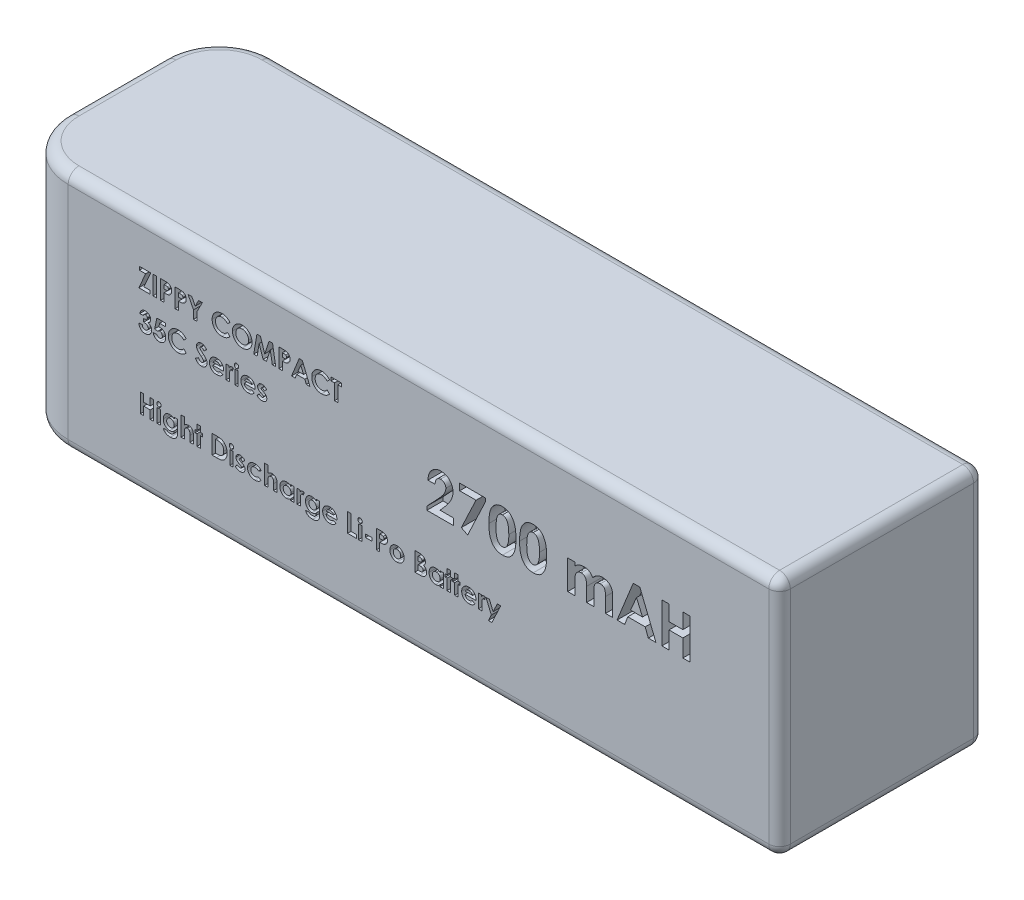
SolidWorks part; units mm, degrees
material "PPS"
ref_plane "Plan de face" through (0, 0, 0) normal (0, 0, 1) x (1, 0, 0)
ref_plane "Plan de dessus" through (0, 0, 0) normal (0, 1, 0) x (1, 0, 0)
ref_plane "Plan de droite" through (0, 0, 0) normal (1, 0, 0) x (0, 0, -1)
sketch "Esquisse1" plane through (0, 0, 0) normal (0, 0, 1) x (1, 0, 0)
  line L1 (0, 0) -> (142, 0)
  line L2 (0, 0) -> (0, 45)
  line L3 (0, 45) -> (142, 45)
  line L4 (142, 0) -> (142, 45)
  dimension "D1" = 142
  dimension "D2" = 45
extrude "Boss.-Extru.1" add sketch "Esquisse1" along normal blind 38
fillet "Congé2" radius 10 2 edges at (0, 22.5, 38) (0, 22.5, 0)
fillet "Congé3" radius 2 14 edges at (142, 22.5, 0) (142, 0, 19) (76, 0, 0) (2.9289, 0, 2.9289) (2.9289, 0, 35.0711) (0, 0, 19) (142, 22.5, 38) (76, 0, 38) (2.9289, 45, 2.9289) (76, 45, 0) (142, 45, 19) (76, 45, 38) (2.9289, 45, 35.0711) (0, 45, 19)
sketch "Esquisse2" plane through (0, 0, 38) normal (0, 0, 1) x (1, 0, 0)
  text T0 "<b>ZIPPY COMPACT</b>\r\n<b>35C Series</b>\r\n\r\n<b>Hight Discharge Li-Po Battery</b>" font "Century Gothic" height 3.5
  text T1 "<b>2700 mAH</b>" font "Century Gothic" height in points 28
extrude "Enlèv. mat.-Extru.1" cut sketch "Esquisse2" against normal blind 3
